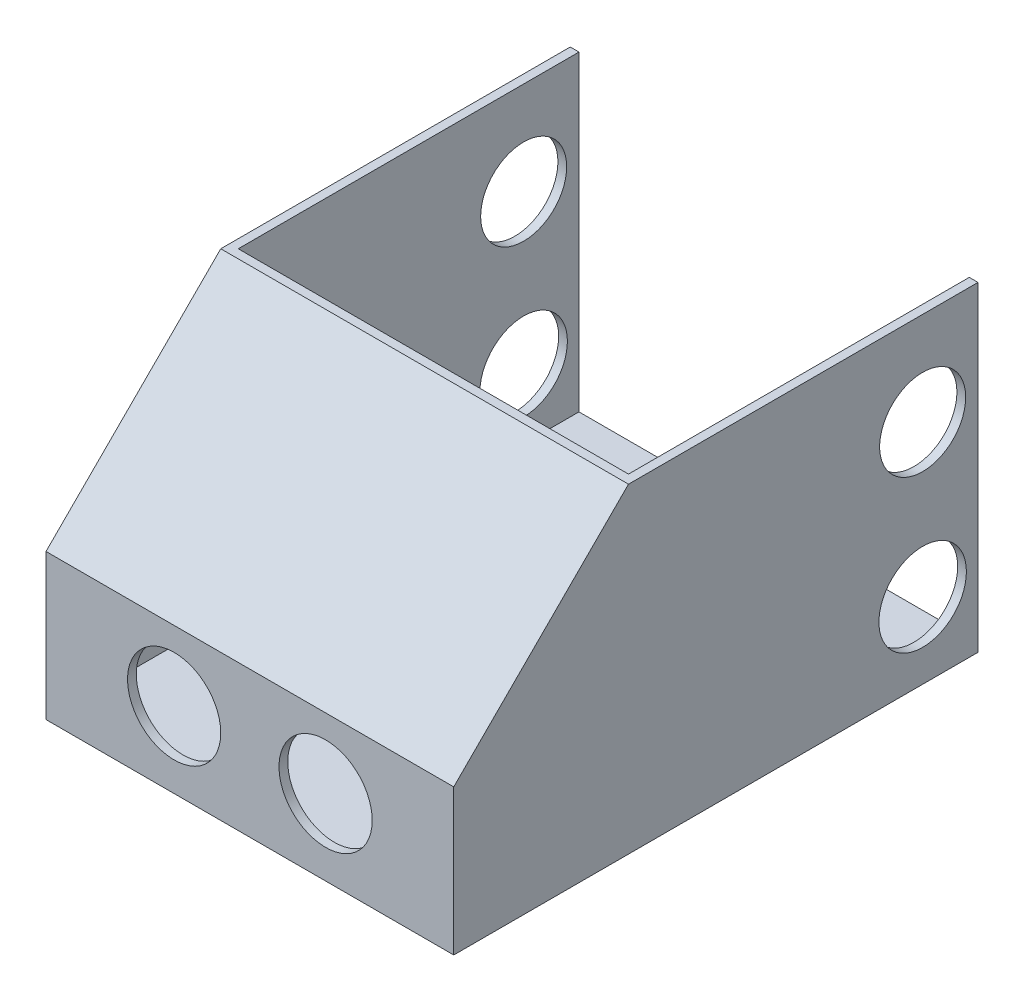
SolidWorks part; units mm, degrees
ref_plane "Plano frontal" through (0, 0, 0) normal (0, 0, 1) x (1, 0, 0)
ref_plane "Plano superior" through (0, 0, 0) normal (0, 1, 0) x (1, 0, 0)
ref_plane "Plano direito" through (0, 0, 0) normal (1, 0, 0) x (0, 0, -1)
sketch "Esboço1" plane through (0, 0, 0) normal (0, 1, 0) x (1, 0, 0)
  line L1 (-35, 45) -> (35, 45)
  line L2 (-35, 45) -> (-35, -45)
  line L3 (-35, -45) -> (35, -45)
  line L4 (35, 45) -> (35, -45)
  line L5 (-35, 45) -> (35, -45) construction
  line L6 (-35, -45) -> (35, 45) construction
  point P0 (0, 0)
  dimension "D1" = 70
  dimension "D2" = 90
extrude "Ressalto-extrusão1" add sketch "Esboço1" along normal blind 55
chamfer "Chanfro1" distance 30 angle 45 1 edges at (0, 55, 45)
sketch "Esboço4" plane through (0, 0, 45) normal (0, 0, 1) x (1, 0, 0)
  line L0 (-35, 0) -> (35, 0) construction
  line L1 (35, 25) -> (35, 0) construction
  line L2 (-35, 25) -> (-35, 0) construction
  circle A0 centre (13, 13) radius 8
  circle A1 centre (-13, 13) radius 8
  dimension "D1" = 16
  dimension "D2" = 16
  dimension "D3" = 13
  dimension "D4" = 13
  dimension "D5" = 22
  dimension "D6" = 22
sketch "Esboço3" plane through (0, 0, -45) normal (0, 0, -1) x (-1, 0, 0)
  line L0 (-35, 55) -> (35, 55) construction
  line L1 (-33.5, 55) -> (33.5, 55)
  line L2 (-33.5, 55) -> (-33.5, 1.5)
  line L3 (-33.5, 1.5) -> (33.5, 1.5)
  line L4 (33.5, 55) -> (33.5, 1.5)
  line L5 (35, 55) -> (35, 0) construction
  line L6 (-35, 0) -> (35, 0) construction
  line L7 (-35, 55) -> (-35, 0) construction
  dimension "D1" = 1.5
  dimension "D2" = 1.5
  dimension "D3" = 1.5
extrude "Corte-extrusão1" cut sketch "Esboço3" against normal blind 58.5
sketch "Esboço5" plane through (0, 0, 13.5) normal (0, 0, -1) x (-1, 0, 0)
  line L0 (33.5, 1.5) -> (33.5, 55) construction
  line L1 (-33.5, 1.5) -> (33.5, 1.5)
  line L2 (-33.5, 1.5) -> (-33.5, 24)
  line L3 (-33.5, 24) -> (33.5, 24)
  line L4 (33.5, 1.5) -> (33.5, 24)
  dimension "D1" = 22.5
extrude "Corte-extrusão3" cut sketch "Esboço5" against normal blind 30
chamfer "Chanfro2" distance 31 angle 45 1 edges at (0, 24, 13.5)
extrude "Corte-extrusão4" cut sketch "Esboço4" against normal through all contours A1 | A0
sketch "Esboço6" plane through (35, 0, 0) normal (1, 0, 0) x (0, 0, -1)
  line L0 (-45, 0) -> (45, 0) construction
  line L1 (45, 55) -> (45, 0) construction
  circle A0 centre (35.5, 13) radius 7.5095
  circle A1 centre (35.5, 39) radius 7.3827
  dimension "D1" = 13
  dimension "D2" = 26
  dimension "D3" = 9.5
  dimension "D4" = 9.5
extrude "Corte-extrusão5" cut sketch "Esboço6" against normal through all
